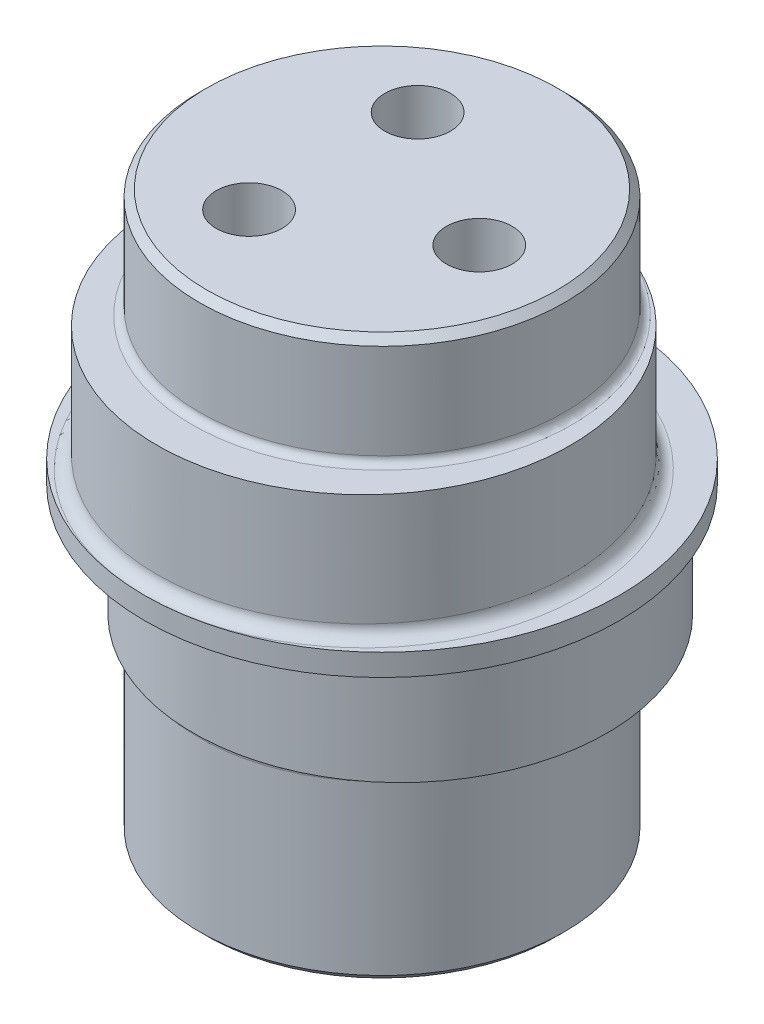
SolidWorks part; units mm, degrees
ref_plane "Front Plane" through (0, 0, 0) normal (0, 0, 1) x (1, 0, 0)
ref_plane "Top Plane" through (0, 0, 0) normal (0, 1, 0) x (1, 0, 0)
ref_plane "Right Plane" through (0, 0, 0) normal (1, 0, 0) x (0, 0, -1)
sketch "Sketch1" plane through (0, 0, 0) normal (0, 1, 0) x (1, 0, 0)
  line L0 (0, 0) -> (0, 0.75) construction
  circle A0 centre (0, 0.75) radius 8.5
  dimension "D1" = 17
  dimension "D2" = 0.75
extrude "Boss-Extrude1" add sketch "Sketch1" along normal blind 5
sketch "Sketch2" plane through (0, 5, 0) normal (0, 1, 0) x (1, 0, 0)
  line L0 (0, 0) -> (0, -0.75) construction
  circle A0 centre (0, -0.75) radius 8.5
  dimension "D2" = 17
  dimension "D1" = 0.75
extrude "Boss-Extrude2" add sketch "Sketch2" along normal blind 6
sketch "Sketch3" plane through (0, 5, 0) normal (0, 1, 0) x (1, 0, 0)
  circle A0 centre (0, 0) radius 9.75
  dimension "D2" = 19.5
extrude "Boss-Extrude3" add sketch "Sketch3" along normal blind 0.9
sketch "Sketch5" plane through (0, 11, 0) normal (0, 1, 0) x (1, 0, 0)
  circle A0 centre (0, 0) radius 7.5
  dimension "D1" = 15
extrude "Boss-Extrude4" add sketch "Sketch5" along normal blind 4.5
sketch "Sketch6" plane through (0, 0, 0) normal (0, -1, 0) x (1, 0, 0)
  circle A0 centre (0, 0) radius 7.5
  dimension "D1" = 15
extrude "Boss-Extrude5" add sketch "Sketch6" along normal blind 7.5
chamfer "Chamfer1" distance 0.3 angle 45 1 edges at (0, -7.5, -7.5)
fillet "Fillet1" radius 0.3 2 edges at (0, 0, -7.5) (0, 11, 7.5)
fillet "Fillet2" radius 0.5 2 edges at (0, 5.9, 9.25) (0, 5, 7.75)
sketch "Sketch7" plane through (0, -7.5, 0) normal (0, -1, 0) x (1, 0, 0)
  circle A0 centre (0, 0) radius 4 construction
  circle A1 centre (4, 0) radius 1.35
  circle A2 centre (-2, -3.4641) radius 1.35
  circle A3 centre (-2, 3.4641) radius 1.35
  point P11 (0, 0)
  dimension "D1" = 8
  dimension "D2" = 2.7
  dimension "D3" = 3
extrude "Cut-Extrude1" cut sketch "Sketch7" against normal through all
sketch "Sketch8" plane through (0, -7.5, 0) normal (0, -1, 0) x (1, 0, 0)
  circle A0 centre (-2, 3.4641) radius 2.8
  circle A1 centre (4, 0) radius 2.8
  circle A2 centre (-2, -3.4641) radius 2.8
  point P10 (0, 0)
  dimension "D1" = 5.6
  dimension "D2" = 3
extrude "Cut-Extrude2" cut sketch "Sketch8" against normal blind 3 draft 1.5
chamfer "Chamfer2" distance 0.3 angle 45 1 edges at (0, 15.5, 7.5)
